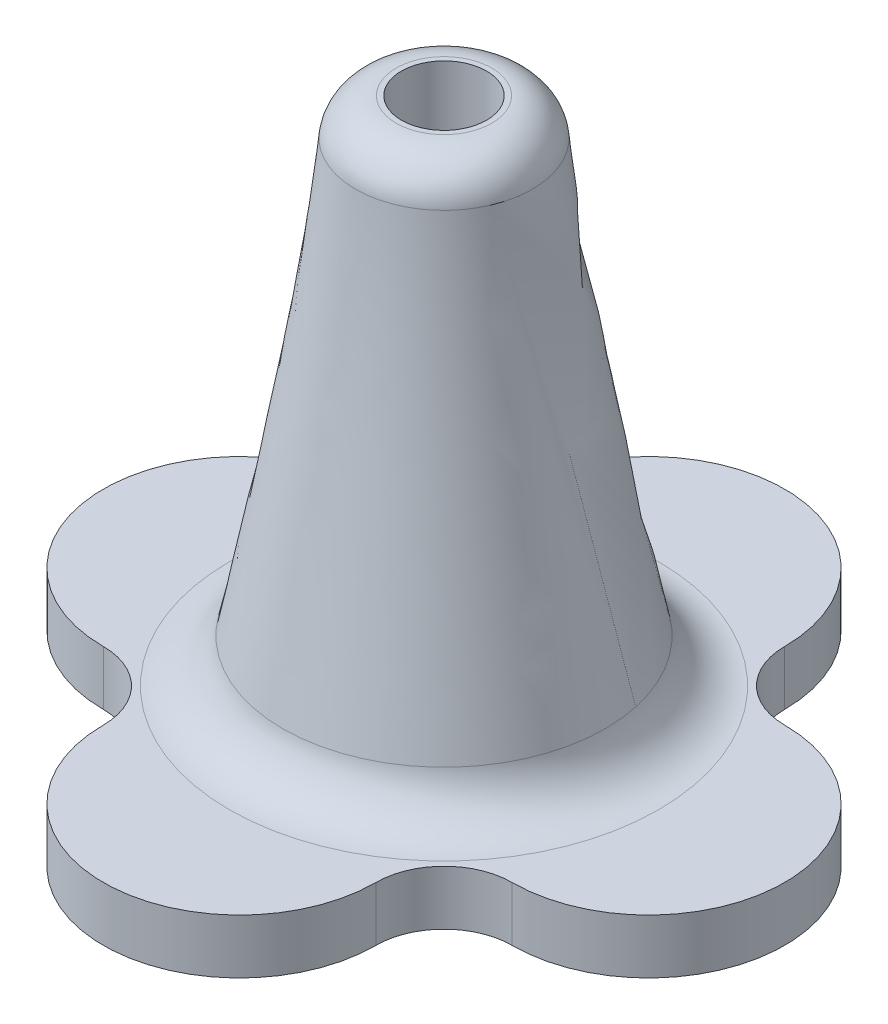
SolidWorks part; units mm, degrees
material "ABS"
ref_plane "Front Plane" through (0, 0, 0) normal (0, 0, 1) x (1, 0, 0)
ref_plane "Top Plane" through (0, 0, 0) normal (0, 1, 0) x (1, 0, 0)
ref_plane "Right Plane" through (0, 0, 0) normal (1, 0, 0) x (0, 0, -1)
sketch "Sketch1" plane through (0, 0, 0) normal (0, 1, 0) x (1, 0, 0)
  line L0 (0, -7.62) -> (0, 7.62) construction
  line L1 (-12.7, -12.7) -> (12.7, -12.7) construction
  line L2 (-12.7, -12.7) -> (-12.7, 12.7) construction
  line L3 (-12.7, 12.7) -> (12.7, 12.7) construction
  line L4 (12.7, -12.7) -> (12.7, 12.7) construction
  line L5 (-12.7, -12.7) -> (12.7, 12.7) construction
  line L6 (-12.7, 12.7) -> (12.7, -12.7) construction
  line L7 (-5.08, -7.62) -> (-5.08, -5.08)
  line L8 (5.08, -7.62) -> (5.08, -5.08)
  line L9 (-7.62, 0) -> (7.62, 0) construction
  line L10 (-7.62, 5.08) -> (-5.08, 5.08)
  line L11 (-7.62, -5.08) -> (-5.08, -5.08)
  line L12 (5.08, 5.08) -> (7.62, 5.08)
  line L13 (-5.08, 5.08) -> (-5.08, 7.62)
  line L14 (5.08, -5.08) -> (7.62, -5.08)
  line L15 (5.08, 5.08) -> (5.08, 7.62)
  arc A0 (-5.08, -7.62) -> (5.08, -7.62) centre (0, -7.62) ccw
  arc A1 (5.08, 7.62) -> (-5.08, 7.62) centre (0, 7.62) ccw
  arc A2 (-7.62, 5.08) -> (-7.62, -5.08) centre (-7.62, 0) ccw
  arc A3 (7.62, -5.08) -> (7.62, 5.08) centre (7.62, 0) ccw
  point P0 (0, 0)
  point P8 (0, 0)
  point P15 (0, 0)
  dimension "D5" = 5.08
  dimension "D8" = 5.08
  dimension "D6" = 5.08
  dimension "D7" = 5.08
  dimension "D1" = 25.4
  dimension "D2" = 25.4
  dimension "D3" = 10.16
  dimension "D4" = 10.16
extrude "Boss-Extrude1" add sketch "Sketch1" along normal blind 2.032
fillet "Fillet1" radius 2.54 4 edges at (-5.08, 1.016, -5.08) (-5.08, 1.016, 5.08) (5.08, 1.016, 5.08) (5.08, 1.016, -5.08)
sketch "Sketch2" plane through (0, 2.032, 0) normal (0, 1, 0) x (1, 0, 0)
  circle A0 centre (0, 0) radius 6.35
  dimension "D1" = 12.7
ref_plane "Plane1" through (0, 21.082, 0) normal (0, 1, 0) x (1, 0, 0)
sketch "Sketch3" plane through (0, 21.082, 0) normal (0, 1, 0) x (1, 0, 0)
  circle A0 centre (0, 0) radius 3.175
  dimension "D1" = 6.35
loft "Loft1" add profiles "Sketch2", "Sketch3" connector at (6.1651, 2.032, -1.5211) connector at (2.7871, 21.082, 1.5208)
sketch "Sketch4" plane through (0, 21.082, 0) normal (0, 1, 0) x (1, 0, 0)
  circle A0 centre (0, 0) radius 1.5875
  dimension "D1" = 3.175
extrude "Cut-Extrude1" cut sketch "Sketch4" against normal up to surface (19.05 mm away) up to face at (0, 2.032, 0)
fillet "Fillet5" [suppressed] radius 1.5875 tangent propagation no
sketch "Sketch5" plane through (0, 2.032, 0) normal (0, 1, 0) x (1, 0, 0)
  line L0 (0, -16.975) -> (0, 16.975) construction
  line L1 (0, 0) -> (8.2637, 0) construction
  circle A0 centre (0, 8.89) radius 2.54
  circle A1 centre (0, 8.89) radius 3.937 construction
  arc A2 (5.08, 7.62) -> (-5.08, 7.62) centre (0, 7.62) ccw construction
  circle A3 centre (0, -8.89) radius 3.937 construction
  circle A4 centre (0, -8.89) radius 2.54
  circle A5 centre (0, 8.89) radius 2.4003 construction
  point P5 (0, 0)
  dimension "D1" = 5.08
  dimension "D2" = 7.874
  dimension "D4" = 4.8006
  dimension "D3" = 1.27
extrude "Cut-Extrude2" [suppressed] cut sketch "Sketch5" against normal up to surface (2.032 mm away) up to face at (0, 0, 0)
fillet "Fillet6" radius 2.032 1 edges at (0, 2.032, 6.35)
fillet "Fillet7" radius 1.524 1 edges at (0, 21.082, 3.175)
equation "\"D6@Sketch1\"=\"D8@Sketch1\""
equation "\"D7@Sketch1\"=\"D5@Sketch1\""
